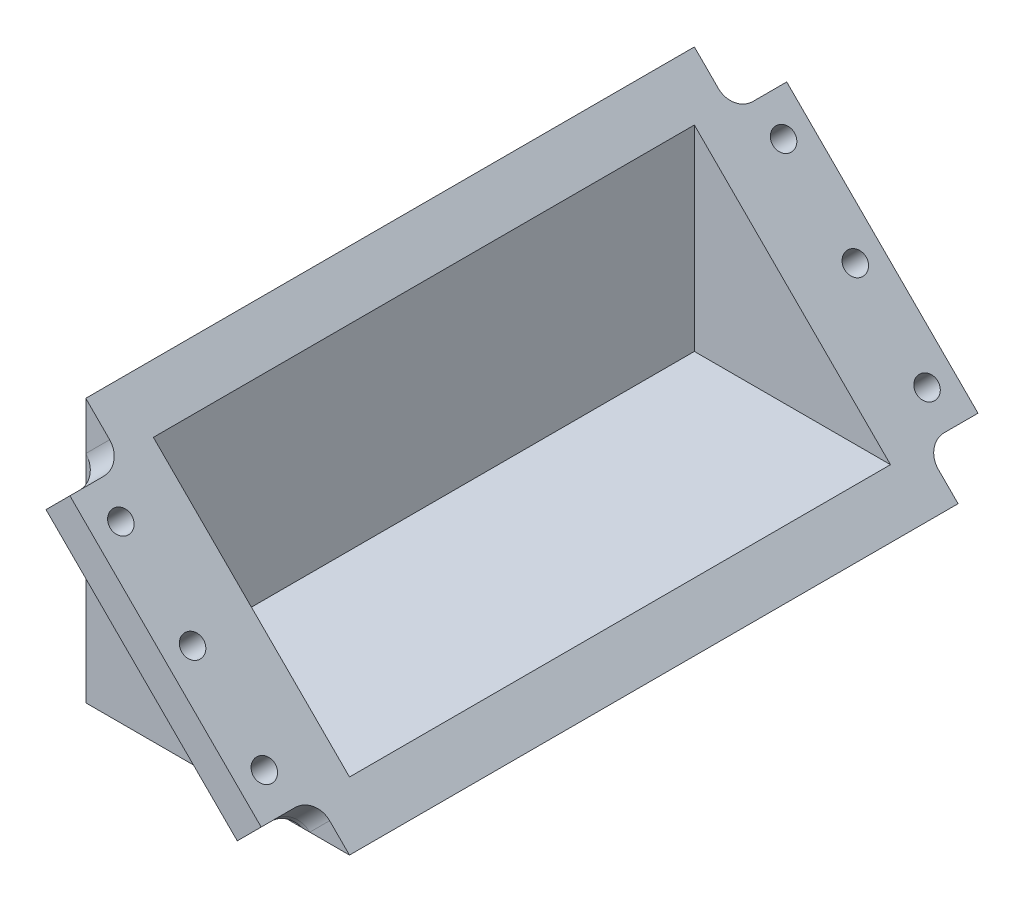
SolidWorks part; units mm, degrees
ref_plane "前视基准面" through (0, 0, 0) normal (0, 0, 1) x (1, 0, 0)
ref_plane "上视基准面" through (0, 0, 0) normal (0, 1, 0) x (1, 0, 0)
ref_plane "右视基准面" through (0, 0, 0) normal (1, 0, 0) x (0, 0, -1)
other "Configuration Table"
sketch "草图2" plane through (0, 0, 0) normal (0, 0, 1) x (1, 0, 0)
  line L0 (0, 0) -> (29, 0)
  line L2 (0, 29) -> (0, 0)
  line L3 (0, 29) -> (-5, 34)
  line L4 (-5, 34) -> (-5, -5)
  line L5 (-5, -5) -> (34, -5)
  line L6 (34, -5) -> (29, 0)
  dimension "D1" = 29
  dimension "D2" = 45
  dimension "D3" = 45
  dimension "D4" = 5
  dimension "D5" = 5
  dimension "D6" = 29
extrude "凸台-拉伸1" add sketch "草图2" along normal mid plane 90
sketch "草图3" plane through (0, 0, -45) normal (0, 0, -1) x (-1, 0, 0)
  line L0 (0, 29) -> (0, 0)
  line L1 (0, 0) -> (-29, 0)
  line L2 (-29, 0) -> (0, 29)
extrude "凸台-拉伸2" add sketch "草图3" against normal blind 5
sketch "草图4" plane through (0, 0, 45) normal (0, 0, 1) x (1, 0, 0)
  line L0 (0, 29) -> (0, 0)
  line L1 (0, 0) -> (29, 0)
  line L2 (29, 0) -> (0, 29)
extrude "凸台-拉伸3" add sketch "草图4" against normal blind 5
sketch "草图5" plane through (14.5, 14.5, 0) normal (0.7071, 0.7071, 0) x (0.7071, -0.7071, 0)
  line L0 (27.5772, 45) -> (-27.5772, 45) construction
  line L1 (-19.5772, 45) -> (20.4228, 45)
  line L2 (-19.5772, 45) -> (-19.5772, 53)
  line L3 (-19.5772, 53) -> (20.4228, 53)
  line L4 (20.4228, 45) -> (20.4228, 53)
  line L5 (-27.5772, 0) -> (27.5772, 0) construction
  line L6 (-27.5772, -45) -> (-27.5772, 45) construction
  line L7 (27.5772, -45) -> (27.5772, 45) construction
  line L8 (-19.5772, 49) -> (20.4228, 49) construction
  line L9 (-19.5772, -49) -> (20.4228, -49) construction
  line L10 (20.4228, -45) -> (20.4228, -53)
  line L11 (-19.5772, -53) -> (20.4228, -53)
  line L12 (-19.5772, -45) -> (-19.5772, -53)
  line L13 (-19.5772, -45) -> (20.4228, -45)
  circle A0 centre (-14.5772, 49) radius 1.6
  circle A1 centre (0.4228, 49) radius 1.6
  circle A2 centre (15.4228, 49) radius 1.6
  circle A3 centre (15.4228, -49) radius 1.6
  circle A4 centre (0.4228, -49) radius 1.6
  circle A5 centre (-14.5772, -49) radius 1.6
  point P21 (0.4228, 49)
  dimension "D4" = 3.2
  dimension "D5" = 15
  dimension "D6" = 15
  dimension "D1" = 8
  dimension "D2" = 8
  dimension "D3" = 40
extrude "凸台-拉伸4" add sketch "草图5" against normal blind 5
fillet "圆角1" radius 3 2 edges at (27.1734, -1.7089, 45) (-1.1109, 26.5754, 45)
fillet "圆角2" radius 3 2 edges at (27.1734, -1.7089, -45) (-1.1109, 26.5754, -45)
